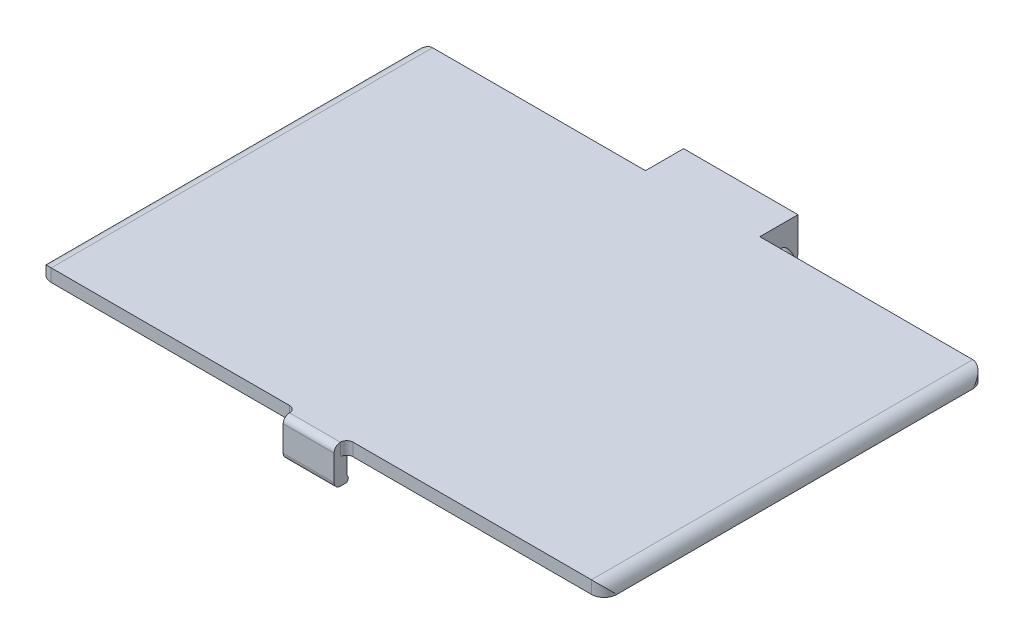
SolidWorks part; units mm, degrees
ref_plane "Přední rovina" through (0, 0, 0) normal (0, 0, 1) x (1, 0, 0)
ref_plane "Horní rovina" through (0, 0, 0) normal (0, 1, 0) x (1, 0, 0)
ref_plane "Pravá rovina" through (0, 0, 0) normal (1, 0, 0) x (0, 0, -1)
sketch "Sketch1" plane through (0, 0, 0) normal (0, 1, 0) x (1, 0, 0)
  line L0 (0, 30) -> (89, 30) construction
  line L1 (0, 0) -> (89, 0)
  line L2 (0, 0) -> (0, 60)
  line L3 (0, 60) -> (89, 60)
  line L4 (89, 0) -> (89, 60)
  line L5 (40.5, 0) -> (48.5, 0)
  line L6 (40.5, 0) -> (40.5, -1)
  line L7 (40.5, -1) -> (48.5, -1)
  line L8 (48.5, 0) -> (48.5, -1)
  line L9 (40.5, 61) -> (48.5, 61)
  line L10 (48.5, 60) -> (48.5, 61)
  line L11 (40.5, 60) -> (48.5, 60)
  line L12 (40.5, 60) -> (40.5, 61)
  point P9 (44.5, 0)
  point P10 (44.5, 0)
  dimension "D1" = 60
  dimension "D2" = 89
  dimension "D3" = 1
  dimension "D4" = 8
extrude "Boss-Extrude1" add sketch "Sketch1" along normal blind 2 contours L2 L0 L4 L3 | L0 L2 L1 L4 | L2 L1 L4 L3 region at (44.5, 0, -45) region at (44.5, 0, -15)
fillet "Fillet6" radius 2 4 edges at (0, 1, 0) (0, 1, -60) (89, 1, -60) (89, 1, 0)
fillet "Fillet8" radius 2 2 edges at (89, 2, -30) (0, 2, -30) tangent propagation no
sketch "Sketch3" plane through (0, 0, -60) normal (0, 0, -1) x (-1, 0, 0)
  line L0 (-44.5, 2) -> (-44.5, 0) construction
  line L1 (-2, 2) -> (-87, 2) construction
  line L2 (-2, 0) -> (-87, 0) construction
  line L4 (-53.5, 2) -> (-35.5, 2)
  line L5 (-53.5, 2) -> (-53.5, -6)
  line L6 (-53.5, -6) -> (-35.5, -6)
  line L7 (-35.5, 2) -> (-35.5, -6)
  line L8 (-51.5, -6) -> (-37.5, -6)
  line L9 (-51.5, -6) -> (-51.5, 0)
  line L10 (-51.5, 0) -> (-37.5, 0)
  line L11 (-37.5, -6) -> (-37.5, 0)
  point P10 (-44.5, 2)
  point P16 (-44.5, 0)
  line M10 (-87, 0) -> (-2, 0)
  line M12 (-2, 2) -> (-87, 2)
  dimension "D1" = 6
  dimension "D2" = 18
  dimension "D3" = 2
extrude "Boss-Extrude2" add sketch "Sketch3" along normal blind 6 contours L6 L9 L5 M10 | L0 L4 L5 M10 | L0 L10 L7 M12 M10 | L11 L6 L7 M10 region at (40, 1, -60) region at (49, 1, -60) region at (52.5, -3, -60) region at (36.5, -3, -60)
ref_plane "Plane1" through (44.5, 0, 0) normal (-1, 0, 0) x (0, 0, 1)
sketch "Sketch7" plane through (35.5, 0, 0) normal (-1, 0, 0) x (0, 0, 1)
  line L0 (-63, 2) -> (-63, -6) construction
  line L1 (-66, 2) -> (-60, 2) construction
  line L2 (-66, -6) -> (-60, -6) construction
  line L3 (-60, -3) -> (-66, -3) construction
  line L4 (-60, 0) -> (-60, -6) construction
  line L5 (-66, 2) -> (-66, -6) construction
  line L6 (-63, -1.2) -> (-63, -4.8)
  arc A0 (-63, -1.2) -> (-63, -4.8) centre (-63, -3) ccw
  dimension "D1" = 1.8
revolve "Revolve2" add sketch "Sketch7" angle 180 about L0 reverse direction yes
mirror "Mirror2" about plane through (44.5, 0, 0) normal (-1, 0, 0) of "Revolve2"
sketch "Sketch5" plane through (0, 0, 0) normal (0, 0, 1) x (1, 0, 0)
  line L0 (44.5, 2) -> (44.5, 0) construction
  line L1 (2, 2) -> (87, 2) construction
  line L2 (2, 0) -> (87, 0) construction
  line L4 (40.5, 2) -> (48.5, 2)
  line L5 (40.5, 2) -> (40.5, -4)
  line L6 (40.5, -4) -> (48.5, -4)
  line L7 (48.5, 2) -> (48.5, -4)
  point P10 (44.5, 2)
  dimension "D1" = 8
  dimension "D2" = 6
extrude "Boss-Extrude3" add sketch "Sketch5" along normal blind 2
fillet "Fillet19" radius 1 4 edges at (44.5, 2, 2) (40.5, 1, 0) (48.5, 1, 0) (44.5, -4, 2)
fillet "Fillet20" radius 3 3 edges at (52.5, -6, -60) (52.5, -6, -66) (36.5, -6, -66)
sketch "Sketch8" plane through (40.5, 0, 0) normal (-1, 0, 0) x (0, 0, 1)
  line L0 (0, 0) -> (0, -4) construction
  line L1 (1, -4) -> (0, -4) construction
  line L2 (0, -3) -> (0, -4)
  arc A0 (0, -4) -> (0, -3) centre (0.4, -3.5) cw
  dimension "D1" = 0.4
  dimension "D2" = 1
extrude "Boss-Extrude4" add sketch "Sketch8" against normal up to surface (8 mm away) up to face at (48.5, -1.1429, 1.0592)
